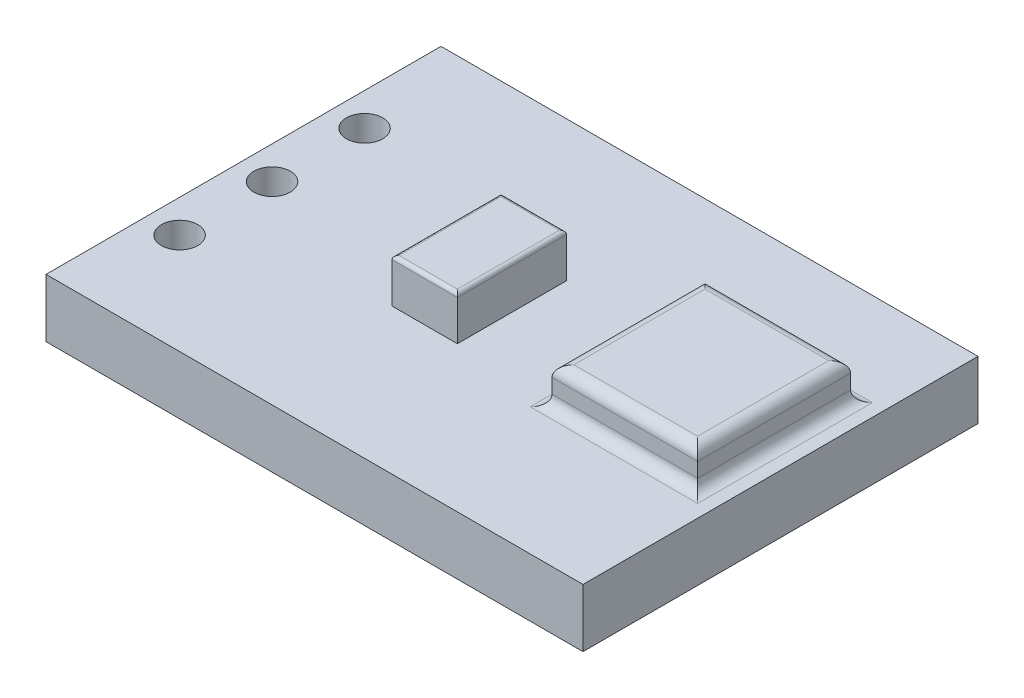
SolidWorks part; units mm, degrees
ref_plane "Front Plane" through (0, 0, 0) normal (0, 0, 1) x (1, 0, 0)
ref_plane "Top Plane" through (0, 0, 0) normal (0, 1, 0) x (1, 0, 0)
ref_plane "Right Plane" through (0, 0, 0) normal (1, 0, 0) x (0, 0, -1)
sketch "Sketch1" plane through (0, 0, 0) normal (0, 1, 0) x (1, 0, 0)
  line L1 (-354.4329, -12.0183) -> (-339.6829, -12.0183)
  line L2 (-354.4329, -12.0183) -> (-354.4329, -1.1683)
  line L3 (-354.4329, -1.1683) -> (-339.6829, -1.1683)
  line L4 (-339.6829, -12.0183) -> (-339.6829, -1.1683)
  dimension "D1" = 14.75
  dimension "D2" = 10.85
extrude "Mic Board" add sketch "Sketch1" along normal blind 1.6
sketch "Sketch2" plane through (0, 1.6, 0) normal (0, 1, 0) x (1, 0, 0)
  line L6 (-339.6829, -1.1683) -> (-354.4329, -1.1683) construction
  line L9 (-353.5329, -1.1683) -> (-353.5329, -4.1683) construction
  line L10 (-353.5329, -4.1683) -> (-354.4329, -4.1683) construction
  line L13 (-354.4329, -1.1683) -> (-354.4329, -12.0183) construction
  circle A0 centre (-353.5329, -4.1683) radius 0.5
  circle A1 centre (-353.5329, -6.7083) radius 0.5
  circle A2 centre (-353.5329, -9.2483) radius 0.5
  dimension "D1" = 3
  dimension "D4" = 1
  dimension "D2" = 3
  dimension "D3" = 0.9
extrude "Pins" cut sketch "Sketch2" against normal up to surface (1.6 mm away) contours A0 | A2 | A1 up to face at (-347.0579, 0, 6.5933)
sketch "mic Sketch" plane through (0, 1.6, 0) normal (0, 1, 0) x (1, 0, 0)
  line L0 (-342.3329, -4.0183) -> (-342.3329, -1.1683) construction
  line L1 (-344.3329, -4.0183) -> (-340.3329, -4.0183)
  line L2 (-344.3329, -4.0183) -> (-344.3329, -8.2183)
  line L3 (-344.3329, -8.2183) -> (-340.3329, -8.2183)
  line L4 (-340.3329, -4.0183) -> (-340.3329, -8.2183)
  line L5 (-339.6829, -1.1683) -> (-354.4329, -1.1683) construction
  line L6 (-340.3329, -6.1183) -> (-339.6829, -6.1183) construction
  line L7 (-339.6829, -12.0183) -> (-339.6829, -1.1683) construction
  dimension "D1" = 2.85
  dimension "D2" = 4
  dimension "D3" = 4.2
  dimension "D4" = 0.65
extrude "Microphone" add sketch "mic Sketch" along normal blind 1 contours L4 L3 L2 L1
sketch "Op Amp Sketch" plane through (0, 1.6, 0) normal (0, 1, 0) x (1, 0, 0)
  line L0 (-348.9329, -12.0183) -> (-348.9329, -8.0183) construction
  line L1 (-354.4329, -12.0183) -> (-339.6829, -12.0183) construction
  line L2 (-348.9329, -6.5183) -> (-354.4329, -6.5183) construction
  line L3 (-348.9329, -8.0183) -> (-347.1329, -8.0183)
  line L4 (-348.9329, -8.0183) -> (-348.9329, -5.0183)
  line L5 (-348.9329, -5.0183) -> (-347.1329, -5.0183)
  line L6 (-347.1329, -8.0183) -> (-347.1329, -5.0183)
  line L7 (-354.4329, -1.1683) -> (-354.4329, -12.0183) construction
  dimension "D1" = 3
  dimension "D2" = 1.8
  dimension "D3" = 4
  dimension "D4" = 5.5
extrude "Op Amp" add sketch "Op Amp Sketch" along normal blind 1.2
fillet "Mic Fillet" radius 0.3 8 edges at (-342.3329, 1.6, 4.0183) (-344.3329, 1.6, 6.1183) (-342.3329, 1.6, 8.2183) (-340.3329, 1.6, 6.1183) (-342.3329, 2.6, 4.0183) (-340.3329, 2.6, 6.1183) (-342.3329, 2.6, 8.2183) (-344.3329, 2.6, 6.1183)
fillet "Op Amp Fillet" radius 0.1 4 edges at (-348.0329, 2.8, 5.0183) (-347.1329, 2.8, 6.5183) (-348.0329, 2.8, 8.0183) (-348.9329, 2.8, 6.5183)
